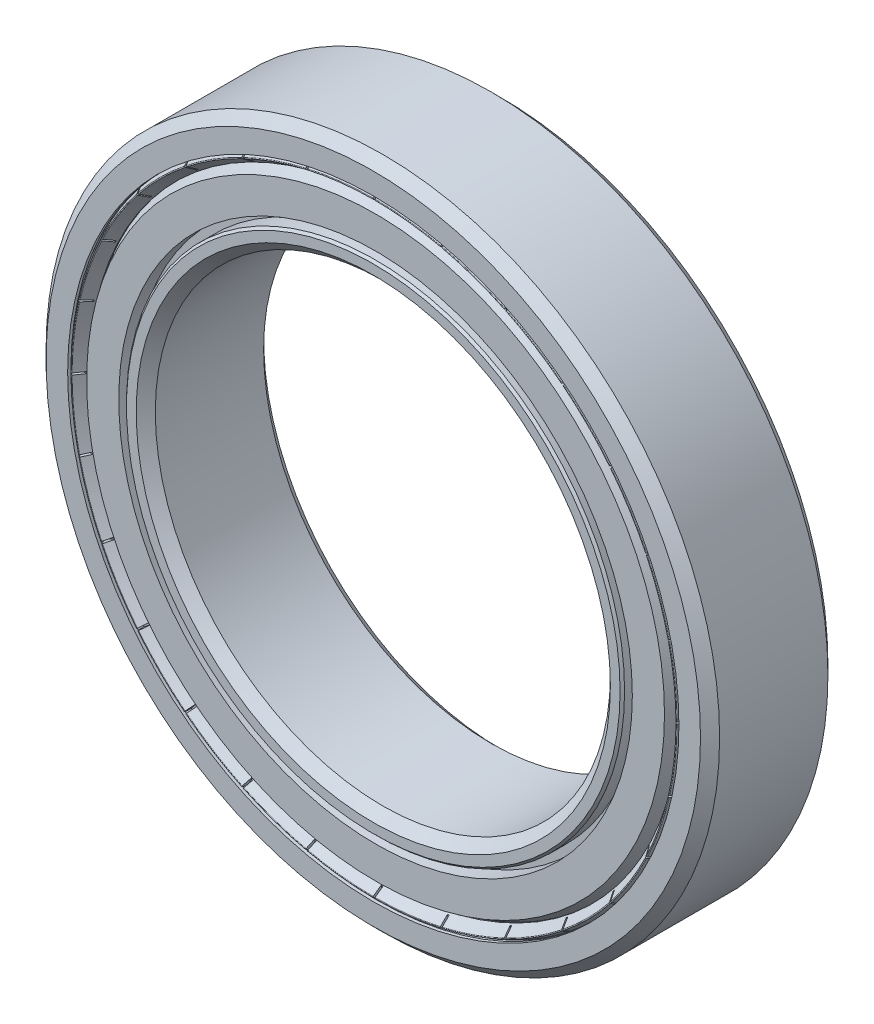
SolidWorks part; units mm, degrees
ref_plane "Front Plane" through (0, 0, 0) normal (0, 0, 1) x (1, 0, 0)
ref_plane "Top Plane" through (0, 0, 0) normal (0, 1, 0) x (1, 0, 0)
ref_plane "Right Plane" through (0, 0, 0) normal (1, 0, 0) x (0, 0, -1)
sketch "Sketch1" plane through (0, 0, 0) normal (0, 0, 1) x (1, 0, 0)
  circle A0 centre (0, 0) radius 12.5
  circle A1 centre (0, 0) radius 18.5
  dimension "OD" = 37
  dimension "ID" = 25
sketch "Sketch2" plane through (0, 0, 0) normal (1, 0, 0) x (0, 0, -1)
  line L0 (-3.5, 18.5) -> (3.5, 18.5)
  line L1 (-3.5, 12.5) -> (-3.5, -12.5) construction
  line L2 (3.5, 18.5) -> (3.5, -18.5) construction
  line L3 (-3.5, 0) -> (3.5, 0) construction
  line L6 (0, 18.5) -> (0, 12.5) construction
  circle A0 centre (0, 15.5) radius 2.1 construction
  point P8 (0, 18.5)
  dimension "Approx. Ball Dia." = 4.2
  dimension "Width" = 7
  dimension "For Shaft Diameter" = 25
  dimension "For Housing ID" = 37
sketch "Sketch3" plane through (0, 0, 0) normal (1, 0, 0) x (0, 0, -1)
  line L0 (0, 0) -> (0, 25) construction
  line L1 (-3.5, 12.5) -> (-3.5, -12.5) construction
  line L2 (2.975, 18.5) -> (-2.975, 18.5)
  line L3 (-2.975, 18.5) -> (-3.5, 17.975)
  line L4 (-3.5, 17.975) -> (-3.5, 16.7898)
  line L5 (-3.5, 16.7898) -> (-3.325, 16.7898)
  line L6 (-3.325, 16.7898) -> (-3.325, 17.1949)
  line L7 (-3.325, 17.1949) -> (-3.2013, 17.3187)
  line L8 (-3.2013, 17.3187) -> (-1.05, 17.3187)
  line L10 (-3.5, 18.5) -> (3.5, 18.5) construction
  line L12 (-3.325, 17.1949) -> (-3.325, 17.6) construction
  line L13 (3.2013, 17.3187) -> (1.05, 17.3187)
  line L14 (3.325, 17.1949) -> (3.2013, 17.3187)
  line L15 (3.325, 16.7898) -> (3.325, 17.1949)
  line L16 (3.5, 16.7898) -> (3.325, 16.7898)
  line L17 (3.5, 17.975) -> (3.5, 16.7898)
  line L18 (2.975, 18.5) -> (3.5, 17.975)
  line L19 (2.975, 12.5) -> (-2.975, 12.5)
  line L20 (-2.975, 12.5) -> (-3.5, 13.025)
  line L21 (-3.5, 13.025) -> (-3.5, 13.5576)
  line L22 (-3.5, 13.5576) -> (-3.3763, 13.6813)
  line L23 (-3.3763, 13.6813) -> (-1.05, 13.6813)
  line L25 (3.3763, 13.6813) -> (1.05, 13.6813)
  line L26 (3.5, 13.5576) -> (3.3763, 13.6813)
  line L27 (3.5, 13.025) -> (3.5, 13.5576)
  line L28 (2.975, 12.5) -> (3.5, 13.025)
  circle A2 centre (0, 15.5) radius 2.1 construction
  arc A3 (-1.05, 17.3187) -> (1.05, 17.3187) centre (0, 15.5) cw
  arc A4 (-1.05, 13.6813) -> (1.05, 13.6813) centre (0, 15.5) ccw
  point P5 (0, 17.6)
  point P31 (0, 18.5)
  point P37 (0, 12.5)
  dimension "D1" = 45
  dimension "D2" = 0.175
  dimension "D3" = 2.1
  dimension "D4" = 0.525
revolve "Revolve1" add sketch "Sketch3" angle 360 about L3
sketch "Sketch4" plane through (0, 0, 0) normal (1, 0, 0) x (0, 0, -1)
  line L0 (0, 17.6) -> (0, 13.4)
  line L1 (0, 18.5) -> (0, 12.5) construction
  circle A0 centre (0, 15.5) radius 2.1 construction
  arc A1 (0, 13.4) -> (0, 17.6) centre (0, 15.5) cw
revolve "Revolve2" add sketch "Sketch4" angle 360 about L6
pattern_circular "CirPattern1" count 14 over 360 about axis through (0, 0, 3.5) along (0, 0, -1) of bodies 106
sketch "Sketch5" plane through (0, 0, 0) normal (1, 0, 0) x (0, 0, -1)
  line L0 (-2.1, 15.5) -> (-2.1, 13.6813) construction
  line L1 (-3.3763, 13.6813) -> (-1.05, 13.6813) construction
  line L3 (-2.1, 13.6813) -> (-2.5254, 13.6813)
  line L4 (-2.5254, 13.6813) -> (-2.5254, 14.1068)
  line L5 (-2.5254, 14.1068) -> (-3.3763, 14.1068)
  line L6 (-3.3763, 14.1068) -> (-3.3763, 15.8732)
  line L7 (-3.3763, 15.8732) -> (-2.5254, 16.3644)
  line L8 (-2.5254, 16.3644) -> (-2.1, 16.3644)
  line L9 (-2.1, 16.3644) -> (-2.1, 13.6813)
  line L10 (0, 15.5) -> (0, 18.5) construction
  line L11 (2.5254, 16.3644) -> (2.1, 16.3644)
  line L12 (3.3763, 15.8732) -> (2.5254, 16.3644)
  line L13 (3.3763, 14.1068) -> (3.3763, 15.8732)
  line L14 (2.5254, 14.1068) -> (3.3763, 14.1068)
  line L15 (2.5254, 13.6813) -> (2.5254, 14.1068)
  line L16 (2.1, 13.6813) -> (2.5254, 13.6813)
  line L17 (2.1, 16.3644) -> (2.1, 13.6813)
  line L18 (-3.3763, 15.8732) -> (-2.9508, 15.8732) construction
  line L19 (-2.9508, 15.8732) -> (-2.5254, 15.8732) construction
  line L20 (-2.5254, 15.8732) -> (-2.1, 15.8732) construction
  line L21 (-2.5254, 16.3644) -> (-2.5254, 16.7898) construction
  circle A0 centre (0, 15.5) radius 2.1 construction
  dimension "D1" = 30
revolve "Revolve3" add sketch "Sketch5" angle 360 about L3
sketch "Sketch6" plane through (0, 0, 0) normal (1, 0, 0) x (0, 0, -1)
  line L0 (-2.7978, 16.7898) -> (-3.1937, 16.7898)
  line L1 (-3.1937, 16.7898) -> (-3.5, 16.613)
  line L2 (-3.5, 16.613) -> (-2.9028, 16.1948)
  line L4 (-3.3763, 15.8732) -> (-2.5254, 16.3644) construction
  line L5 (-2.7978, 16.2072) -> (-2.7978, 16.7898)
  line L6 (-3.5, 16.7898) -> (-3.325, 16.7898) construction
  line L7 (-2.9028, 16.1948) -> (-2.8678, 16.1948)
  line L8 (-2.8678, 16.1948) -> (-2.7978, 16.2072)
  line L9 (-3.5, 17.975) -> (-3.5, -17.975) construction
  line L11 (-2.8678, 16.1948) -> (-2.8328, 16.1948) construction
  line L12 (-2.8328, 16.1948) -> (-2.7978, 16.1948) construction
  point P27 (-2.9958, 16.7898)
  dimension "D1" = 30
  dimension "D3" = 10
  dimension "D2" = 35
  dimension "D4" = 0.035
  dimension "D5" = 0.3062
revolve "Revolve4" add sketch "Sketch6" angle 360 about L3
fillet "Fillet1" radius 0.035 1 edges at (16.613, 0, 3.5)
sketch "Sketch7" plane through (0, 0, 0) normal (0, 0, 1) x (1, 0, 0)
  line L0 (-0.05, 16.7898) -> (-0.05, 16.8898)
  line L1 (-0.05, 16.7898) -> (0.05, 16.7898) construction
  line L2 (-0.05, 16.7898) -> (-0.05, 16.1948)
  line L3 (-0.05, 16.1948) -> (0.05, 16.1948) construction
  line L4 (0.05, 16.7898) -> (0.05, 16.1948)
  line L5 (-0.05, 16.8898) -> (0.05, 16.8898)
  line L6 (0.05, 16.8898) -> (0.05, 16.7898)
  line L7 (-0.05, 16.1948) -> (-0.05, 16.0948)
  line L8 (-0.05, 16.0948) -> (0.05, 16.0948)
  line L9 (0.05, 16.0948) -> (0.05, 16.1948)
  dimension "D1" = 0.1
extrude "Cut-Extrude1" cut sketch "Sketch7" along normal through all from vertex starting at point (0, 16.7898, 2.9958)
pattern_circular "CirPattern2" count 28 over 360 about axis through (0, 0, 3.5) along (0, 0, -1) of "Cut-Extrude1"
mirror "Mirror1" about plane through (0, 0, 0) normal (0, 0, 1) of bodies 120
equation "\"Approx. Ball Dia.@Sketch2\"=( \"OD@Sketch1\" - \"ID@Sketch1\" )  * .5 * .7"
equation "\"D2@Sketch3\"=\"Width@Sketch2\"*.025"
equation "\"D3@Sketch3\"=\"Approx. Ball Dia.@Sketch2\"*.5"
equation "\"D4@Sketch3\"=\"Width@Sketch2\"*.075"
equation "\"Approx No of Balls\"= ( pi * \"OD@Sketch1\" ) * .5 / \"Approx. Ball Dia.@Sketch2\""
equation "\"D1@CirPattern1\"=\"Approx No of Balls\""
equation "\"D4@Sketch6\"=\"D2@Sketch3\"*.2"
equation "\"D1@CirPattern2\"=\"Approx No of Balls\"*2"
equation "\"D5@Sketch6\"=\"D2@Sketch3\"*1.75"
equation "\"D1@Fillet1\"=\"d4@sketch6\""
